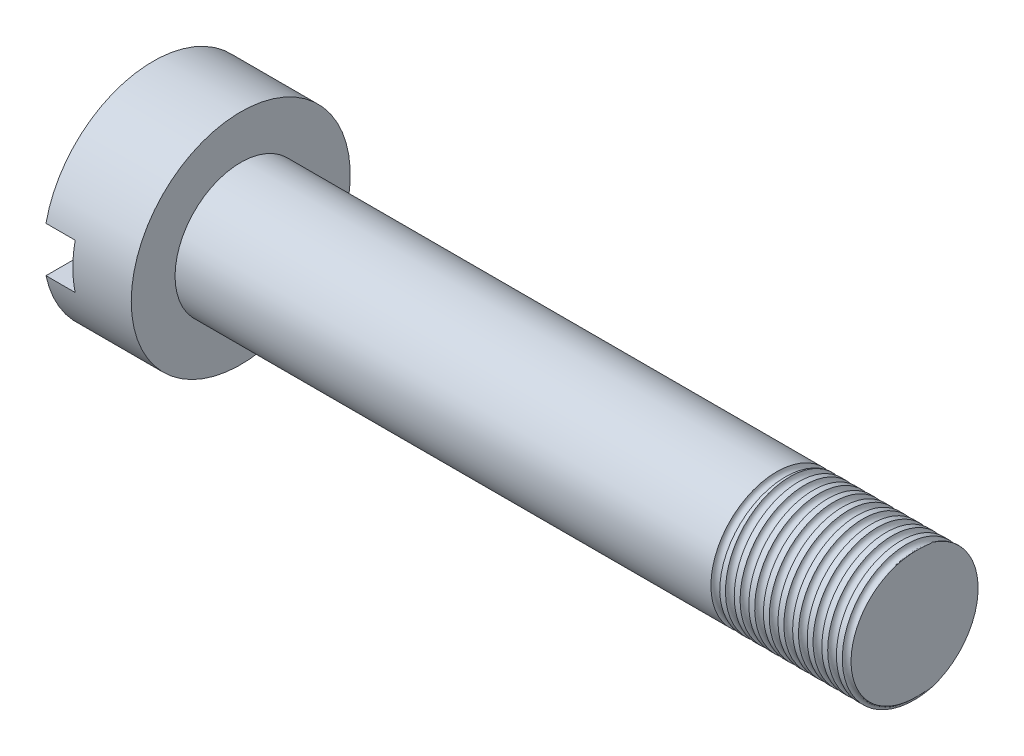
SolidWorks part; units mm, degrees
material "Alloy Steel"
ref_plane "Front Plane" through (0, 0, 0) normal (0, 0, 1) x (1, 0, 0)
ref_plane "Top Plane" through (0, 0, 0) normal (0, 1, 0) x (1, 0, 0)
ref_plane "Right Plane" through (0, 0, 0) normal (1, 0, 0) x (0, 0, -1)
sketch "Sketch1" plane through (0, 0, 0) normal (0, 0, 1) x (1, 0, 0)
  line L0 (0.8597, 0) -> (23, 0)
  line L1 (23, 0) -> (23, 2.25)
  line L2 (23, 2.25) -> (0, 2.25)
  line L3 (0, 2.25) -> (0, 3.75)
  line L4 (0, 3.75) -> (-3, 3.75)
  line L5 (-3, 3.75) -> (-3, 0)
  line L6 (-3, 0) -> (0.8597, 0)
  point P8 (0, 0)
  point P9 (0, 0)
  point P10 (0, 0)
  point P11 (-0.0575, 0)
  dimension "D1" = 2.25
  dimension "D2" = 26
  dimension "D3" = 3
  dimension "D4" = 1.5
revolve "Revolve1" add sketch "Sketch1" angle 360 about L6
sketch "Sketch2" plane through (-3, 0, 0) normal (-1, 0, 0) x (0, 0, 1)
  line L1 (-3.75, -0.7756) -> (3.75, -0.7756)
  line L2 (-3.75, -0.7756) -> (-3.75, 0.7756)
  line L3 (-3.75, 0.7756) -> (3.75, 0.7756)
  line L4 (3.75, -0.7756) -> (3.75, 0.7756)
  circle A0 centre (0, 0) radius 3.75 construction
  point P5 (0, 0)
  point P6 (0, 0)
  point P7 (0, 0.8455)
  point P8 (3.75, 0)
  point P10 (0, 0.7756)
  point P11 (-6.0035, -0.4571)
extrude "Cut-Extrude1" cut sketch "Sketch2" against normal blind 1
sketch "Sketch4" plane through (23, 0, 0) normal (1, 0, 0) x (0, 0, -1)
  circle A0 centre (0, 0) radius 2.25
curve "Helix/Spiral1" pitch 0.5 height 4.5 turns 9
ref_plane "Plane1" through (0, 0, 0) normal (0, 1, 0) x (1, 0, 0)
sketch "Sketch11" plane through (0, 0, 0) normal (0, 1, 0) x (1, 0, 0)
  circle A0 centre (23, -2.25) radius 0.15
  dimension "D1" = 0.3
sweep "Cut-Sweep1" cut profiles "Sketch11" path "Helix/Spiral1" align with end faces yes
sketch "Sketch12" plane through (0, 0, 0) normal (0, 1, 0) x (1, 0, 0)
  line L0 (25.3004, 0) -> (-5.7132, 0) construction
sketch "Sketch13" plane through (0, 0, 0) normal (0, -1, 0) x (-1, 0, 0)
  circle A0 centre (-18.5007, -2.2488) radius 0.1507
revolve "Cut-Revolve2" cut sketch "Sketch13" angle 360 about L0
